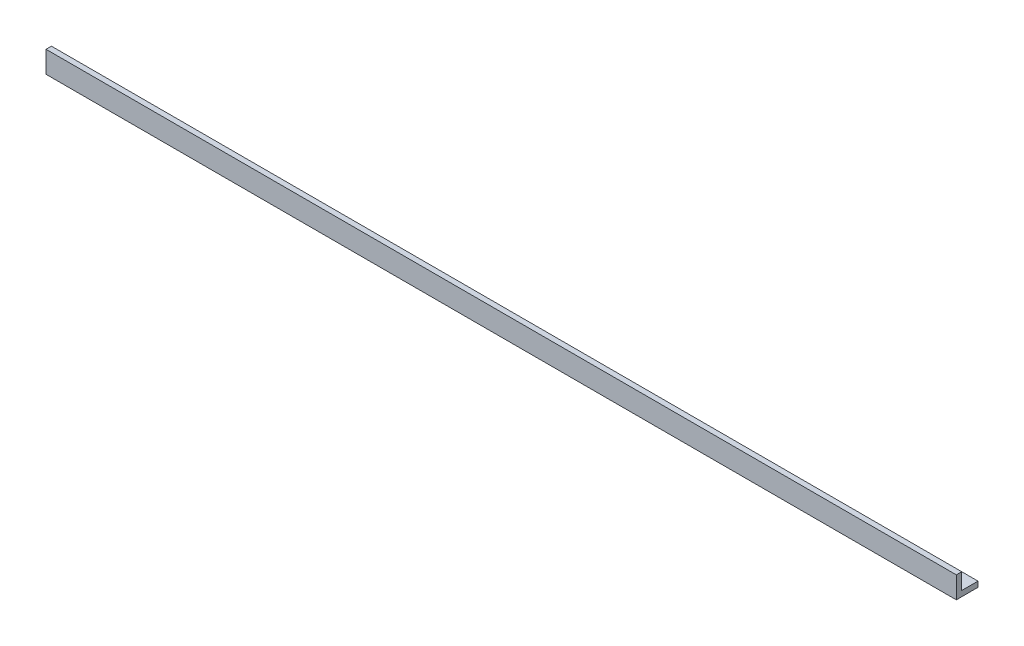
SolidWorks part; units mm, degrees
material "6061-T6 (SS)"
ref_plane "Front Plane" through (0, 0, 0) normal (0, 0, 1) x (1, 0, 0)
ref_plane "Top Plane" through (0, 0, 0) normal (0, 1, 0) x (1, 0, 0)
ref_plane "Right Plane" through (0, 0, 0) normal (1, 0, 0) x (0, 0, -1)
sketch "Sketch1" plane through (0, 0, 0) normal (1, 0, 0) x (0, 0, -1)
  line L0 (0, 25.4) -> (0, 0)
  line L1 (0, 0) -> (25.4, 0)
  line L2 (6.35, 25.4) -> (6.35, 6.35)
  line L3 (6.35, 6.35) -> (25.4, 6.35)
  line L4 (0, 25.4) -> (6.35, 25.4)
  line L5 (25.4, 6.35) -> (25.4, 0)
  dimension "D1" = 25.4
  dimension "D2" = 6.35
extrude "Boss-Extrude1" add sketch "Sketch1" along normal blind 533.4 and the other way blind 533.4 contours L5 L3 L2 L4 L0 L1 region at (0, 25.0408, -3.175)
